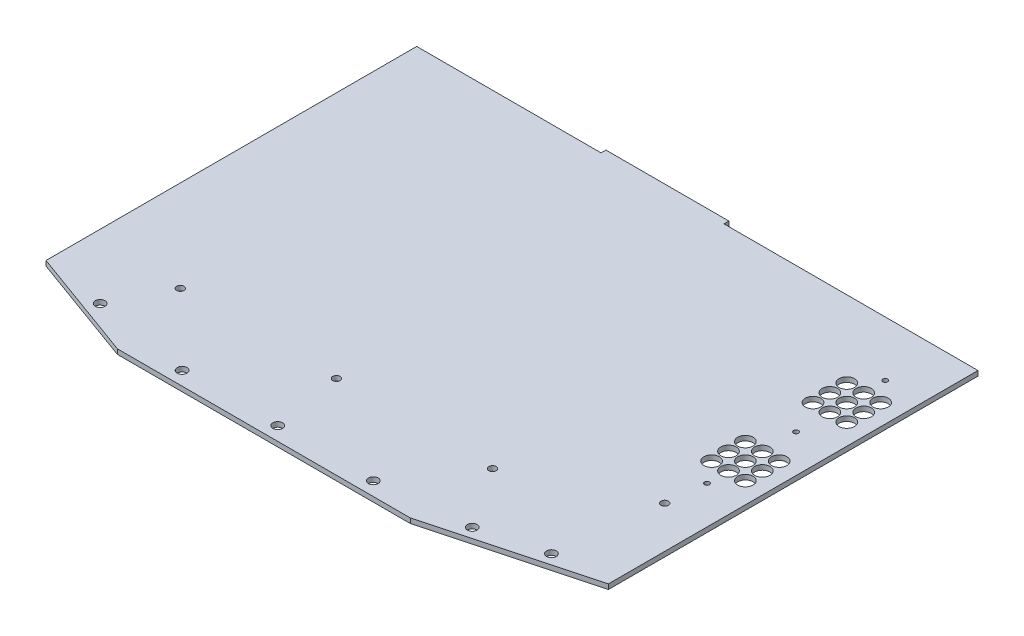
SolidWorks part; units mm, degrees
material "6061-T6 (SS)"
ref_plane "X-Y Datum" through (0, 0, 0) normal (0, 0, 1) x (1, 0, 0)
ref_plane "X-Z Datum" through (0, 0, 0) normal (0, 1, 0) x (1, 0, 0)
ref_plane "Y-Z Datum" through (0, 0, 0) normal (1, 0, 0) x (0, 0, -1)
sketch "Sketch1" plane through (0, 0, 0) normal (0, 0, 1) x (1, 0, 0)
  line L1 (-154.0408, -1.5875) -> (154.0408, -1.5875)
  line L2 (-154.0408, -1.5875) -> (-154.0408, 1.5875)
  line L3 (-154.0408, 1.5875) -> (154.0408, 1.5875)
  line L4 (154.0408, -1.5875) -> (154.0408, 1.5875)
  line L5 (-154.0408, -1.5875) -> (154.0408, 1.5875) construction
  line L6 (-154.0408, 1.5875) -> (154.0408, -1.5875) construction
  point P0 (0, 0)
  dimension "D1" = 3.175
  dimension "D2" = 308.0817
extrude "Boss-Extrude1" add sketch "Sketch1" along normal blind 267.83
sketch "Sketch3" plane through (154.0408, 0, 0) normal (1, 0, 0) x (0, 0, -1)
  line L9 (0, -1.5875) -> (0, 1.5875)
  line L10 (0, 1.5875) -> (-267.83, 1.5875)
  line L11 (-267.83, 1.5875) -> (-267.83, -1.5875)
  line L12 (-267.83, -1.5875) -> (0, -1.5875)
  line L13 (0, -1.5875) -> (0, 1.5875)
  line L14 (0, 1.5875) -> (-267.83, 1.5875)
  line L15 (-267.83, 1.5875) -> (-267.83, -1.5875)
  line L16 (-267.83, -1.5875) -> (0, -1.5875)
  dimension "D1" = 0
extrude "Boss-Extrude3" add sketch "Sketch3" along normal blind 3.175
sketch "Sketch4" plane through (0, 0, 267.83) normal (0, 0, 1) x (1, 0, 0)
  line L1 (157.2158, -1.5875) -> (208.1047, -1.5875)
  line L2 (157.2158, -1.5875) -> (157.2158, 1.5875)
  line L3 (157.2158, 1.5875) -> (208.1047, 1.5875)
  line L4 (208.1047, -1.5875) -> (208.1047, 1.5875)
  dimension "D1" = 3.175
  dimension "D2" = 50.8889
extrude "Boss-Extrude4" add sketch "Sketch4" against normal blind 267.83
sketch "Sketch6" plane through (0, 1.5875, 0) normal (0, 1, 0) x (1, 0, 0)
  line L0 (106.5047, -267.83) -> (106.5047, -223.38)
  line L1 (208.1047, -267.83) -> (-154.0408, -267.83) construction
  line L2 (208.1047, -223.38) -> (106.5047, -223.38)
  line L3 (208.1047, 0) -> (208.1047, -267.83) construction
  line L5 (106.5047, -267.83) -> (208.1047, -240.6064)
  line L7 (-154.0408, -267.83) -> (208.1047, -267.83) construction
  line L8 (208.1047, 0) -> (208.1047, -267.83) construction
  line L9 (208.1047, 0) -> (208.1047, -267.83)
  line M9 (-154.0408, -267.83) -> (208.1047, -267.83)
  line M10 (208.1047, -267.83) -> (208.1047, 0)
  dimension "D1" = 44.45
  dimension "D2" = 101.6
  dimension "D3" = 15
extrude "Cut-Extrude1" cut sketch "Sketch6" against normal through all contours L5 M9 M10 region at (174.2381, 1.5875, 258.7555)
sketch "Sketch11" plane through (0, -1.5875, 0) normal (0, -1, 0) x (1, 0, 0)
  line L0 (-84.1908, 267.83) -> (-84.1908, 242.43)
  line L1 (-154.0408, 267.83) -> (106.5047, 267.83) construction
  line L2 (-154.0408, 242.43) -> (-84.1908, 242.43)
  line L3 (-154.0408, 267.83) -> (-154.0408, 0) construction
  line L4 (-154.0408, 242.43) -> (-84.1908, 267.83)
  line M4 (-154.0408, 267.83) -> (-154.0408, 0)
  line M18 (106.5047, 267.83) -> (-154.0408, 267.83)
  dimension "D1" = 69.85
  dimension "D2" = 25.4
extrude "Cut-Extrude3" cut sketch "Sketch11" against normal through all contours L4 M4 M18 region at (-130.7575, -1.5875, 259.3633)
sketch "Sketch17" plane through (-154.0408, 0, 0) normal (-1, 0, 0) x (0, 0, 1)
  line L16 (0, -1.5875) -> (242.43, -1.5875)
  line L17 (242.43, -1.5875) -> (242.43, 1.5875)
  line L18 (242.43, 1.5875) -> (0, 1.5875)
  line L19 (0, 1.5875) -> (0, -1.5875)
  line L20 (0, -1.5875) -> (242.43, -1.5875)
  line L21 (242.43, -1.5875) -> (242.43, 1.5875)
  line L22 (242.43, 1.5875) -> (0, 1.5875)
  line L23 (0, 1.5875) -> (0, -1.5875)
  dimension "D1" = 0
extrude "Boss-Extrude5" add sketch "Sketch17" along normal blind 3.175
sketch "Sketch23" plane through (0, 1.5875, 0) normal (0, 1, 0) x (1, 0, 0)
  line L0 (-154.0408, -242.43) -> (-157.2158, -241.2755)
  line L2 (-154.0408, -242.43) -> (-84.1908, -267.83) construction
  line L3 (-154.0408, -242.43) -> (-84.1908, -267.83) construction
  line L4 (-157.2158, 0) -> (-157.2158, -242.43) construction
extrude "Cut-Extrude7" cut sketch "Sketch23" against normal through all and the other way through all
sketch "Sketch25" plane through (0, -1.5875, 0) normal (0, -1, 0) x (1, 0, 0)
  line L0 (-157.2289, 241.2707) -> (-83.9953, 267.9011) construction
  line L1 (-50.9753, 267.83) -> (-50.9753, 258.94)
  line L2 (-157.2158, 241.2755) -> (-84.1908, 267.83) construction
  line L3 (-118.0827, 255.5057) -> (-115.3206, 247.91)
  line L5 (-84.1908, 267.83) -> (106.5047, 267.83) construction
  line L6 (-50.9753, 258.94) -> (11.2547, 258.94) construction
  line L7 (11.2547, 258.94) -> (73.4847, 258.94) construction
  line L8 (172.3981, 250.1739) -> (172.5447, 242.093)
  line L9 (106.5047, 267.83) -> (208.1047, 240.6064) construction
  line L10 (172.5447, 242.093) -> (131.9047, 252.9824) construction
  circle A0 centre (-115.3206, 247.91) radius 3.175
  circle A1 centre (-50.9753, 258.94) radius 3.175
  circle A2 centre (11.2547, 258.94) radius 3.175
  circle A3 centre (73.4847, 258.94) radius 3.175
  circle A4 centre (172.5447, 242.093) radius 3.175
  circle A5 centre (131.9047, 252.9824) radius 3.175
  point P7 (0, 0)
  dimension "D2" = 90
  dimension "D3" = 6.35
  dimension "D13" = 8.89
  dimension "D1" = 8.0823
  dimension "D5" = 33.02
  dimension "D6" = 62.23
  dimension "D7" = 62.23
  dimension "D8" = 33.02
  dimension "D9" = 35.56
  dimension "D10" = 73.96
  dimension "D11" = 40.64
  dimension "D12" = 8.0823
extrude "Cut-Extrude8" cut sketch "Sketch25" against normal blind 3.175 contours A0 | A1 | A2 | A5 | A4 | A3 region at (-117.0906, -1.5875, 245.383) region at (-53.1568, -1.5875, 256.7584) region at (11.2547, -1.5875, 258.94) region at (170.3831, -1.5875, 239.8917) region at (131.9047, -1.5875, 252.9824)
sketch "Sketch27" plane through (0, -1.5875, 0) normal (0, -1, 0) x (1, 0, 0)
  circle A0 centre (172.4867, 137.7748) radius 5 construction
  circle A1 centre (172.4867, 137.7748) radius 5
  circle A2 centre (183.4867, 137.7748) radius 5 construction
  circle A3 centre (183.4867, 137.7748) radius 5
  circle A4 centre (194.4867, 137.7748) radius 5 construction
  circle A5 centre (194.4867, 126.7748) radius 5 construction
  circle A6 centre (194.4867, 115.7748) radius 5 construction
  circle A7 centre (183.4867, 126.7748) radius 5 construction
  circle A8 centre (183.4867, 115.7748) radius 5 construction
  circle A9 centre (172.4867, 115.7748) radius 5 construction
  circle A10 centre (172.4867, 126.7748) radius 5 construction
  circle A11 centre (194.4867, 137.7748) radius 5
  circle A12 centre (194.4867, 126.7748) radius 5
  circle A13 centre (194.4867, 115.7748) radius 5
  circle A14 centre (183.4867, 126.7748) radius 5
  circle A15 centre (183.4867, 115.7748) radius 5
  circle A16 centre (172.4867, 115.7748) radius 5
  circle A17 centre (172.4867, 126.7748) radius 5
  circle A18 centre (194.4867, 71.7748) radius 5 construction
  circle A19 centre (194.4867, 60.7748) radius 5 construction
  circle A20 centre (194.4867, 49.7748) radius 5 construction
  circle A21 centre (183.4867, 71.7748) radius 5 construction
  circle A22 centre (183.4867, 60.7748) radius 5 construction
  circle A23 centre (183.4867, 49.7748) radius 5 construction
  circle A24 centre (172.4867, 49.7748) radius 5 construction
  circle A25 centre (172.4867, 60.7748) radius 5 construction
  circle A26 centre (172.4867, 71.7748) radius 5 construction
  circle A27 centre (194.4867, 71.7748) radius 5
  circle A28 centre (194.4867, 60.7748) radius 5
  circle A29 centre (194.4867, 49.7748) radius 5
  circle A30 centre (183.4867, 71.7748) radius 5
  circle A31 centre (183.4867, 60.7748) radius 5
  circle A32 centre (183.4867, 49.7748) radius 5
  circle A33 centre (172.4867, 49.7748) radius 5
  circle A34 centre (172.4867, 60.7748) radius 5
  circle A35 centre (172.4867, 71.7748) radius 5
extrude "Cut-Extrude9" cut sketch "Sketch27" against normal through all
sketch "Sketch30" plane through (0, 0, 0) normal (0, 0, -1) x (-1, 0, 0)
  line L0 (37.216, 1.5875) -> (37.216, -1.5875) construction
  line L1 (-42.784, 1.5875) -> (37.216, 1.5875) construction
  line L2 (-42.784, 1.5875) -> (-42.784, -1.5875) construction
  line L3 (37.216, 1.5875) -> (37.216, -1.5875)
  line L4 (-42.784, 1.5875) -> (37.216, 1.5875)
  line L5 (-42.784, 1.5875) -> (-42.784, -1.5875)
  line L6 (157.2158, -1.5875) -> (-208.1047, -1.5875) construction
  line L7 (157.2158, -1.5875) -> (-208.1047, -1.5875)
  line M1 (157.2158, 1.5875) -> (-208.1047, 1.5875)
  line M3 (-208.1047, -1.5875) -> (157.2158, -1.5875)
extrude "Boss-Extrude6" add sketch "Sketch30" along normal blind 3.175 contours L5 L3 M1 M3 region at (2.784, 0, 0)
sketch "Sketch31" plane through (0, -1.5875, 0) normal (0, -1, 0) x (1, 0, 0)
  circle A0 centre (183.4867, 151.7748) radius 2.4 construction
  circle A1 centre (183.4867, 151.7748) radius 2.4 construction
  circle A2 centre (183.4867, 151.7748) radius 1.5875
  dimension "D1" = 3.175
extrude "Cut-Extrude10" cut sketch "Sketch31" against normal through all both and the other way through all
pattern_linear "LPattern1" count 3 spacing 58 along (0, 0, -1) of "Cut-Extrude10"
sketch "Sketch34" plane through (0, -1.5875, 0) normal (0, -1, 0) x (1, 0, 0)
  point P0 (180.965, 176.776)
  point P1 (-97.7709, 213.285)
  point P2 (3.829, 213.285)
  point P3 (105.4291, 213.285)
hole_wizard "M4 Clearance Hole1" positions "Sketch34" profile "Sketch35" hole size "M4" standard "ANSI Metric" end condition through all
sketch "Sketch35" plane through (180.965, -1.5875, 176.776) normal (1, 0, 0) x (0, 0, -1)
  line L0 (0, 0) -> (0, 3.175)
  line L1 (0, 3.175) -> (2.4, 3.175)
  line L2 (2.4, 3.175) -> (2.4, 0)
  line L5 (2.4, 0) -> (0, 0)
  line L11 (0, -6.35) -> (0, 107.95) construction
  dimension "Thru Hole Dia." = 4.8
  dimension "Thru Hole Depth" = 3.175
